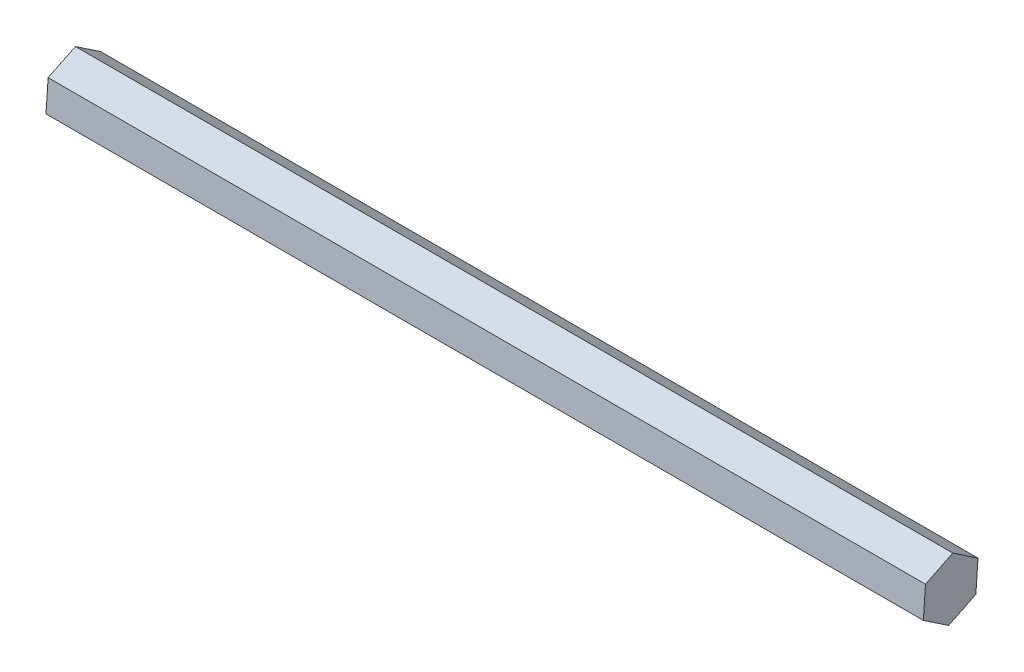
SolidWorks part; units mm, degrees
ref_plane "Front Plane" through (0, 0, 0) normal (0, 0, 1) x (1, 0, 0)
ref_plane "Top Plane" through (0, 0, 0) normal (0, 1, 0) x (1, 0, 0)
ref_plane "Right Plane" through (0, 0, 0) normal (1, 0, 0) x (0, 0, -1)
sketch "Sketch1" plane through (0, 0, 0) normal (1, 0, 0) x (0, 0, -1)
  line L1 (-1.4359, 0.9686) -> (-1.5568, -0.7592)
  line L2 (-1.5568, -0.7592) -> (-0.1209, -1.7278)
  line L3 (-0.1209, -1.7278) -> (1.4359, -0.9686)
  line L4 (1.4359, -0.9686) -> (1.5568, 0.7592)
  line L5 (1.5568, 0.7592) -> (0.1209, 1.7278)
  line L6 (0.1209, 1.7278) -> (-1.4359, 0.9686)
  circle A0 centre (0, 0) radius 1.5 construction
extrude "Boss-Extrude1" add sketch "Sketch1" along normal blind 50
